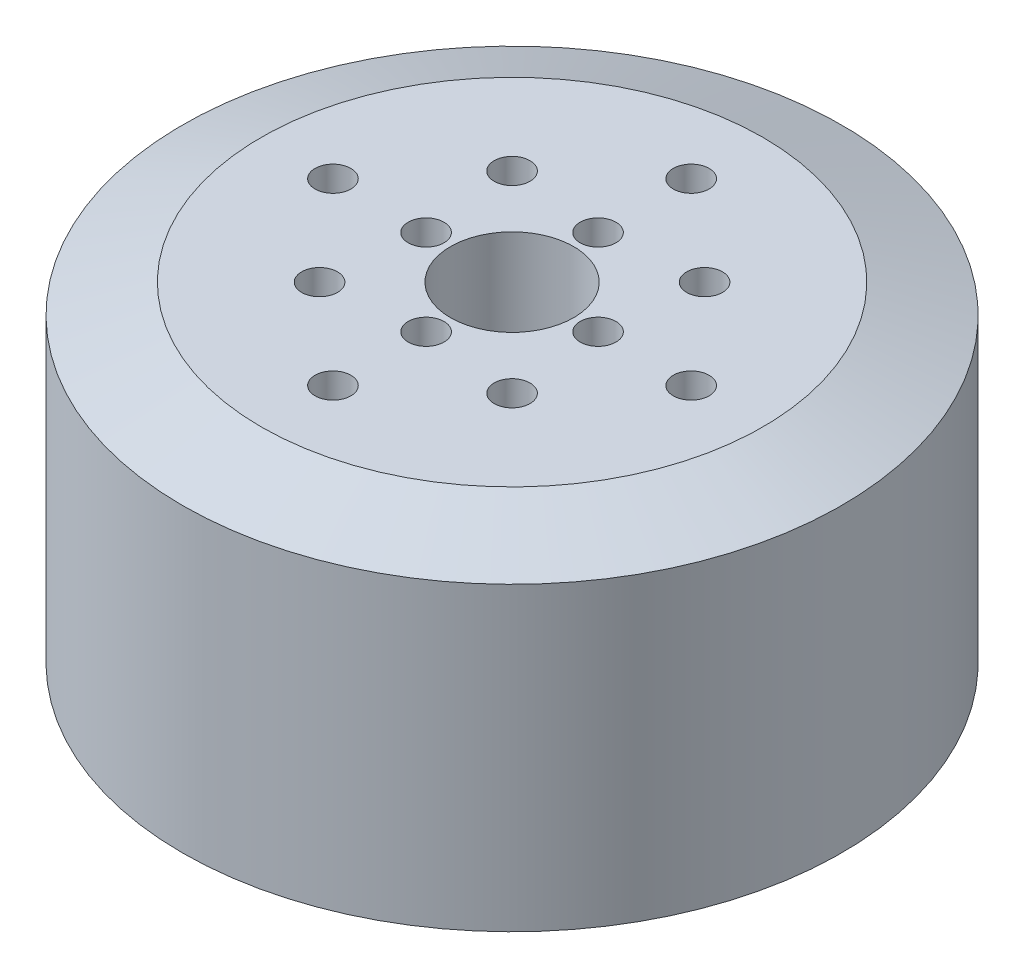
SolidWorks part; units mm, degrees
material "3.1355 (EN-AW 2024)"
ref_plane "Спереди" through (0, 0, 0) normal (0, 0, 1) x (1, 0, 0)
ref_plane "Сверху" through (0, 0, 0) normal (0, 1, 0) x (1, 0, 0)
ref_plane "Справа" through (0, 0, 0) normal (1, 0, 0) x (0, 0, -1)
sketch "Эскиз1" plane through (0, 0, 0) normal (0, 1, 0) x (1, 0, 0)
  circle A0 centre (0, 0) radius 23
  dimension "D1" = 46
extrude "Бобышка-Вытянуть1" add sketch "Эскиз1" along normal blind 23
chamfer "Фаска1" distance 2 angle 70 1 edges at (0, 23, 23) first distance on face at (0, 23, 23)
sketch "Эскиз2" plane through (0, 23, 0) normal (0, 1, 0) x (1, 0, 0)
  circle A0 centre (0, 0) radius 3.5
  circle A1 centre (0, 0) radius 5
  dimension "D1" = 7
  dimension "D2" = 10
extrude "Вырез-Вытянуть1" cut sketch "Эскиз2" against normal through all contours A0 region at (0, 23, 0)
extrude "Бобышка-Вытянуть2" add sketch "Эскиз2<3>" against normal blind 32
sketch "Эскиз2<3>" plane through (0, 23, 0) normal (0, 1, 0) x (1, 0, 0) same geometry as "Эскиз2"
sketch "Эскиз3" plane through (0, 23, 0) normal (0, 1, 0) x (1, 0, 0)
  line L0 (9.5, 0) -> (0, 0) construction
  line L1 (0, 0) -> (6.7175, 6.7175) construction
  line L2 (0, 0) -> (6.7175, -6.7175) construction
  line L3 (0, 0) -> (-6.7175, -6.7175) construction
  line L4 (0, 0) -> (-6.7175, 6.7175) construction
  circle A0 centre (0, 0) radius 6 construction
  circle A1 centre (0, 0) radius 12.5 construction
  circle A2 centre (0, 0) radius 9.5 construction
  point P4 (0, 12.5)
  point P5 (0, -12.5)
  point P6 (-12.5, 0)
  point P7 (12.5, 0)
  point P8 (6, 0)
  point P9 (0, 6)
  point P10 (-6, 0)
  point P11 (0, -6)
  point P21 (0, 0)
  dimension "D1" = 12
  dimension "D2" = 25
  dimension "D3" = 19
  dimension "D4" = 45
  dimension "D5" = 4
sketch "Эскиз4" plane through (0, 0, 0) normal (0, -1, 0) x (1, 0, 0)
  circle A1 centre (0, 0) radius 5 construction
  circle A2 centre (0, 0) radius 21
  circle A3 centre (0, 0) radius 21
  circle A4 centre (0, 0) radius 5
  dimension "D1" = 2
extrude "Вырез-Вытянуть2" cut sketch "Эскиз4" against normal blind 19
hole_wizard "Отверстие обработанное метчиком M3x0.51" positions "Эскиз6" profile "Эскиз5" tap size "M3x0.5" standard "Ansi Metric" end condition through all
sketch "Эскиз6" plane through (0, 23, 0) normal (0, 1, 0) x (1, 0, 0)
  point P0 (0, 12.5)
  point P3 (12.5, 0)
  point P6 (0, -12.5)
  point P9 (-12.5, 0)
sketch "Эскиз5" plane through (0, 23, -12.5) normal (1, 0, 0) x (0, 0, 1)
  line L0 (0, 0) -> (0, 32)
  line L1 (0, 32) -> (1.25, 32)
  line L2 (1.25, 32) -> (1.25, 0)
  line L5 (1.25, 0) -> (0, 0)
  line L11 (0, -6.35) -> (0, 107.95) construction
  dimension "Диаметр проходного сверла" = 2.5
  dimension "Глубина проходного сверла" = 32
cosmetic thread "Отверстие резьбы1" parameters "D2"=3
cosmetic thread "Отверстие резьбы2" parameters "D2"=3
cosmetic thread "Отверстие резьбы3" parameters "D2"=3
cosmetic thread "Отверстие резьбы4" parameters "D2"=3
hole_wizard "Отверстие обработанное метчиком M3x0.52" positions "Эскиз8" profile "Эскиз7" tap size "M3x0.5" standard "Ansi Metric"
sketch "Эскиз8" plane through (0, 23, 0) normal (0, 1, 0) x (1, 0, 0)
  point P0 (6, 0)
  point P2 (0, 6)
  point P5 (-6, 0)
  point P8 (0, -6)
cosmetic thread "Отверстие резьбы5" parameters "D1"=6, "D2"=3
cosmetic thread "Отверстие резьбы6" parameters "D1"=6, "D2"=3
cosmetic thread "Отверстие резьбы7" parameters "D1"=6, "D2"=3
cosmetic thread "Отверстие резьбы8" parameters "D1"=6, "D2"=3
sketch "Эскиз7" plane through (6, 23, 0) normal (1, 0, 0) x (0, 0, 1)
  line L0 (0, 0) -> (0, 8.2511)
  line L1 (0, 8.2511) -> (1.25, 7.5)
  line L2 (1.25, 7.5) -> (1.25, 0)
  line L5 (1.25, 0) -> (0, 0)
  line L10 (0, 8.2511) -> (-1.25, 7.5) construction
  line L11 (0, -6.35) -> (0, 107.95) construction
  dimension "Диаметр сверла" = 2.5
  dimension "Глубина сверла" = 7.5
  dimension "Угол заточки сверла" = 118
sketch "Эскиз9" plane through (0, 23, 0) normal (0, 1, 0) x (1, 0, 0)
  point P3 (0, -6)
  point P5 (6, 0)
hole_wizard "Отверстие обработанное метчиком M3x0.53" positions "Эскиз11" profile "Эскиз10" tap size "M3x0.5" standard "Ansi Metric" end condition through all
sketch "Эскиз11" plane through (0, 23, 0) normal (0, 1, 0) x (1, 0, 0)
  point P0 (-6.7175, 6.7175)
  point P3 (6.7175, 6.7175)
  point P6 (6.7175, -6.7175)
  point P9 (-6.7175, -6.7175)
cosmetic thread "Отверстие резьбы9" parameters "D2"=3
cosmetic thread "Отверстие резьбы10" parameters "D2"=3
cosmetic thread "Отверстие резьбы11" parameters "D2"=3
cosmetic thread "Отверстие резьбы12" parameters "D2"=3
sketch "Эскиз10" plane through (-6.7175, 23, -6.7175) normal (1, 0, 0) x (0, 0, 1)
  line L0 (0, 0) -> (0, 32)
  line L1 (0, 32) -> (1.25, 32)
  line L2 (1.25, 32) -> (1.25, 0)
  line L5 (1.25, 0) -> (0, 0)
  line L11 (0, -6.35) -> (0, 107.95) construction
  dimension "Диаметр проходного сверла" = 2.5
  dimension "Глубина проходного сверла" = 32
sketch "Эскиз12" plane through (0, 23, 0) normal (0, 1, 0) x (1, 0, 0)
  circle A0 centre (0, 0) radius 4.3
  dimension "D1" = 8.6
extrude "Вырез-Вытянуть3" cut sketch "Эскиз12" against normal blind 25
sketch "Эскиз13" plane through (0, 23, 0) normal (0, 1, 0) x (1, 0, 0)
  line L1 (-7.2175, 7.2175) -> (-6.2175, 7.2175)
  line L2 (-7.2175, 7.2175) -> (-7.2175, 6.2175)
  line L3 (-7.2175, 6.2175) -> (-6.2175, 6.2175)
  line L4 (-6.2175, 7.2175) -> (-6.2175, 6.2175)
  line L5 (-7.2175, 7.2175) -> (-6.2175, 6.2175) construction
  line L6 (-7.2175, 6.2175) -> (-6.2175, 7.2175) construction
  point P0 (-6.7175, 6.7175)
  point P1 (6.7175, 6.7175)
  point P3 (6.7175, -6.7175)
  point P5 (-6.7175, 6.7175)
  dimension "D1" = 1
equation "\"D2@Эскиз2\"=\"D1@Эскиз2\"+3"
